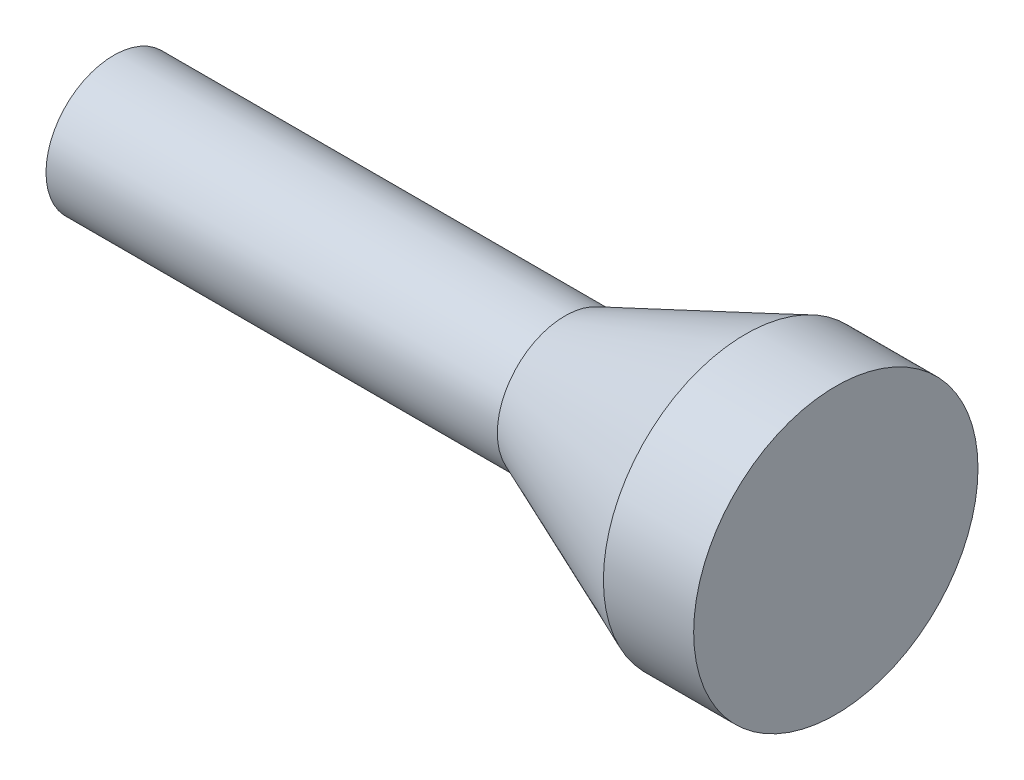
SolidWorks part; units mm, degrees
material "Cast Alloy Steel"
ref_plane "Front Plane" through (0, 0, 0) normal (0, 0, 1) x (1, 0, 0)
ref_plane "Top Plane" through (0, 0, 0) normal (0, 1, 0) x (1, 0, 0)
ref_plane "Right Plane" through (0, 0, 0) normal (1, 0, 0) x (0, 0, -1)
other "Center of Mass"
ref_axis "X" through (-88.99, 0, 0) along (1, 0, 0)
ref_axis "Y" through (0, 55, 0) along (0, -1, 0)
ref_axis "Z" through (0, 0, -88.99) along (0, 0, 1)
sketch "Sketch1" plane through (0, 0, 0) normal (0, 0, 1) x (1, 0, 0)
  line L0 (190.5, 0) -> (190.5, 80.01)
  line L1 (190.5, 80.01) -> (139.7, 80.01)
  line L2 (139.7, 80.01) -> (38.1, 38.1)
  line L3 (38.1, 38.1) -> (-215.9, 38.1)
  line L4 (-215.9, 38.1) -> (-215.9, 0)
  line L5 (-215.9, 0) -> (190.5, 0)
  dimension "D1" = 38.1
  dimension "D2" = 406.4
  dimension "D3" = 80.01
  dimension "D4" = 50.8
  dimension "D5" = 101.6
  dimension "D6" = 38.1
revolve "Revolve1" add sketch "Sketch1" angle 360 about axis through (-88.99, 0, 0) along (1, 0, 0)
